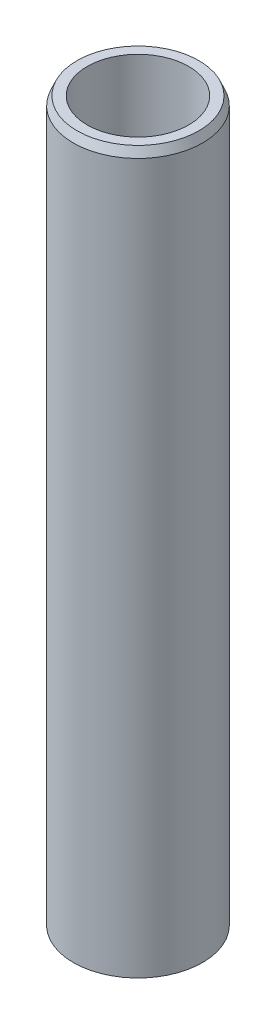
SolidWorks part; units mm, degrees
ref_plane "Front Plane" through (0, 0, 0) normal (0, 0, 1) x (1, 0, 0)
ref_plane "Top Plane" through (0, 0, 0) normal (0, 1, 0) x (1, 0, 0)
ref_plane "Right Plane" through (0, 0, 0) normal (1, 0, 0) x (0, 0, -1)
sketch "Sketch1" plane through (0, 0, 0) normal (0, 1, 0) x (1, 0, 0)
  circle A0 centre (0, 0) radius 32.5
  dimension "SHAFT_OD" = 65
extrude "Boss-Extrude1" add sketch "Sketch1" along normal blind 363.2108
sketch "Sketch2" plane through (0, 0, 0) normal (0, 1, 0) x (1, 0, 0)
  circle A0 centre (0, 0) radius 25.5269
  dimension "BORE_D" = 51.0538
extrude "Cut-Extrude1" cut sketch "Sketch2" along normal through all
chamfer "Chamfer1" distance 4.3605 angle 23.385 2 edges at (0, 363.2108, 32.5) (0, 0, 32.5) first distance on face at (0, 363.2108, 32.5) first distance on face at (0, 0, 25.5269)
